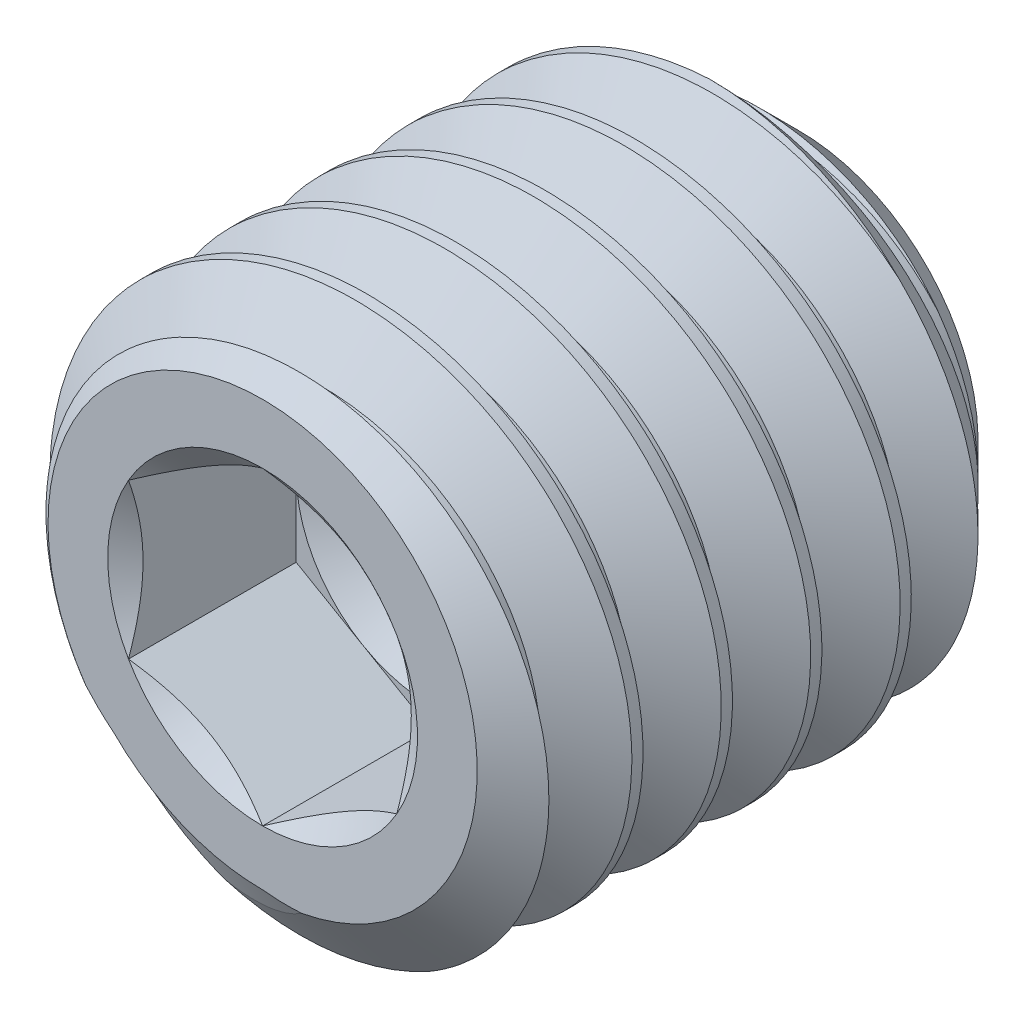
SolidWorks part; units mm, degrees
ref_plane "Front" through (0, 0, 0) normal (0, 0, 1) x (1, 0, 0)
ref_plane "Top" through (0, 0, 0) normal (0, 1, 0) x (1, 0, 0)
ref_plane "Right" through (0, 0, 0) normal (1, 0, 0) x (0, 0, -1)
sketch "Sketch22" plane through (0, 0, 0) normal (1, 0, 0) x (0, 0, -1)
  line L0 (-3, 0) -> (-3, 2.4)
  line L1 (-3, 2.4) -> (-2.5799, 3)
  line L2 (-2.5799, 3) -> (2, 3)
  line L3 (2, 3) -> (3, 2)
  line L4 (-0.2899, 3) -> (-0.2899, -3) construction
  line L5 (3, 0) -> (-3, 0)
  line L6 (-3, 2.4) -> (-3, -2.4) construction
  line L7 (3, 0) -> (3, 2)
  point P11 (-0.2899, 0)
  dimension "Length" = 6
  dimension "D3" = 35
  dimension "D6" = 45
  dimension "Dia" = 6
  dimension "D1" = 4.8
  dimension "D2" = 1
revolve "Revolve1" add sketch "Sketch22" angle 360 about L5
ref_plane "Plane1" through (0, 0, -3) normal (0, 0, 1) x (1, 0, 0)
sketch "Sketch27" plane through (0, 0, -3) normal (0, 0, 1) x (1, 0, 0)
  circle A0 centre (0, 0) radius 3 construction
  circle A1 centre (0, 0) radius 3
curve "Helix/Spiral1" pitch 1 height 7 radius 3 centre (0, 0, -3) axis (0, 0, 1) start towards (0, 1, 0)
sketch "Sketch28" plane through (0, 0, 0) normal (1, 0, 0) x (0, 0, -1)
  line L0 (3, 3) -> (3.875, 3)
  line L1 (3.875, 3) -> (3.5, 2.3505)
  line L2 (3.5, 2.3505) -> (3.375, 2.3505)
  line L3 (3.375, 2.3505) -> (3, 3)
  line L4 (3.1875, 2.6752) -> (3.6875, 2.6752) construction
  line L6 (-2.5799, 3) -> (2, 3) construction
  dimension "D1" = 0.125
  dimension "D3" = 60
  dimension "D2" = 0.5
sweep "Cut-Sweep2" cut profiles "Sketch28" path "Helix/Spiral1" align with end faces yes
sketch "Sketch23" plane through (0, 0, 3) normal (0, 0, 1) x (1, 0, 0)
  line L1 (0, 1.7321) -> (-1.5, 0.866)
  line L2 (-1.5, 0.866) -> (-1.5, -0.866)
  line L3 (-1.5, -0.866) -> (0, -1.7321)
  line L4 (0, -1.7321) -> (1.5, -0.866)
  line L5 (1.5, -0.866) -> (1.5, 0.866)
  line L6 (1.5, 0.866) -> (0, 1.7321)
  circle A0 centre (0, 0) radius 1.5 construction
  dimension "Hex" = 3
extrude "Cut-Extrude10" cut sketch "Sketch23" against normal blind 1.875
sketch "Sketch24" plane through (0, 0, 3) normal (0, 0, 1) x (1, 0, 0)
  circle A0 centre (0, 0) radius 1.7321
extrude "Cut-Extrude11" cut sketch "Sketch24" against normal through all draft 55
sketch "Sketch26" plane through (0, 0, 1.125) normal (0, 0, 1) x (1, 0, 0)
  circle A0 centre (0, 0) radius 1.5 construction
  circle A1 centre (0, 0) radius 1.5
extrude "Cut-Extrude12" cut sketch "Sketch26" against normal through all draft 60
sketch "Sketch30" plane through (0, 0, 0) normal (1, 0, 0) x (0, 0, -1)
  line L0 (-2.5799, 3) -> (2, 3) construction
  line L1 (-3, 0) -> (-3, 2.4) construction
  line L2 (3, 0) -> (3, 2) construction
  point P0 (-3, 3)
  point P1 (3, 3)
  point P2 (3, -3)
  point P11 (0.5, -3)
  dimension "D1" = 2.5
equation "\"D1@Sketch28\" = \"D4@Helix/Spiral1\" * .125"
equation "\"D2@Sketch28\" = \"D4@Helix/Spiral1\" * .5"
equation "\"D3@Helix/Spiral1\" = \"Length@Sketch22\" + \"D4@Helix/Spiral1\""
equation "\"D1@Sketch30\" = \"D4@Helix/Spiral1\" * 2.5"
equation "\"hex Depth@Cut-Extrude10\" = \"Hex@Sketch23\" * .625"
equation "\"D1@Sketch22\" = \"Dia@Sketch22\" * .8"
equation "\"D2@Sketch22\" = \"D4@Helix/Spiral1\""
